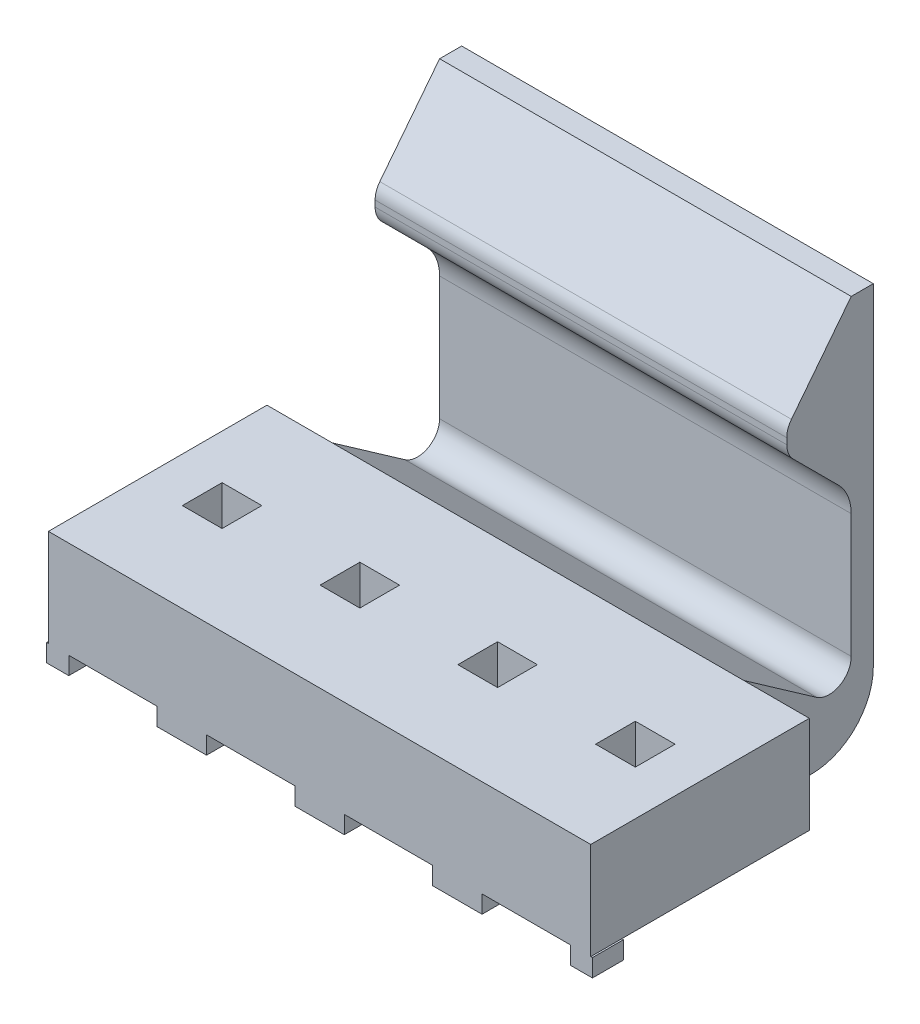
SolidWorks part; units mm, degrees
material "ABS"
ref_plane "Front Plane" through (0, 0, 0) normal (0, 0, 1) x (1, 0, 0)
ref_plane "Top Plane" through (0, 0, 0) normal (0, 1, 0) x (1, 0, 0)
ref_plane "Right Plane" through (0, 0, 0) normal (1, 0, 0) x (0, 0, -1)
sketch "Sketch51" plane through (0, 0, 0) normal (1, 0, 0) x (0, 0, -1)
  line L9 (3.1433, 1.397) -> (3.1432, -1.397)
  line L42 (-3.1432, -1.397) -> (3.1432, -1.397)
  line L44 (3.1433, 1.397) -> (-3.1433, 1.397)
  line L45 (-3.1433, 1.397) -> (-3.1432, -1.397)
  dimension "D1" = 2.794
  dimension "D2" = 6.2865
extrude "Boss-Extrude23" add sketch "Sketch51" along normal mid plane 15.6 separate body
sketch "Sketch49" plane through (0, 1.397, 0) normal (0, 1, 0) x (1, 0, 0)
  line L0 (7.8, 0) -> (5.9858, 0) construction
  line L1 (7.8, 3.1433) -> (7.8, -3.1433) construction
  line L16 (1.4097, -0.575) -> (2.5527, -0.575)
  line L17 (2.5527, -0.575) -> (2.5527, 0.568)
  line L18 (2.5527, 0.568) -> (1.4097, 0.568)
  line L19 (1.4097, 0.568) -> (1.4097, -0.575)
  line L20 (5.3721, -0.575) -> (6.5151, -0.575)
  line L21 (6.5151, -0.575) -> (6.5151, 0.568)
  line L22 (6.5151, 0.568) -> (5.3721, 0.568)
  line L23 (5.3721, 0.568) -> (5.3721, -0.575)
  line L24 (-2.5527, -0.575) -> (-1.4097, -0.575)
  line L25 (-1.4097, -0.575) -> (-1.4097, 0.568)
  line L26 (-1.4097, 0.568) -> (-2.5527, 0.568)
  line L27 (-2.5527, 0.568) -> (-2.5527, -0.575)
  line L28 (-6.5151, -0.575) -> (-5.3721, -0.575)
  line L29 (-5.3721, -0.575) -> (-5.3721, 0.568)
  line L30 (-5.3721, 0.568) -> (-6.5151, 0.568)
  line L31 (-6.5151, 0.568) -> (-6.5151, -0.575)
  line L34 (1.4097, -0.0035) -> (-1.4097, -0.0035) construction
  line L35 (0, 0) -> (0, -0.0035) construction
  dimension "D2" = 1.143
  dimension "D4" = 2.8194
  dimension "D5" = 2.8194
  dimension "D6" = 2.8194
extrude "Cut-Extrude22" cut sketch "Sketch49" against normal through all
sketch "Sketch50" plane through (0, 0, 0) normal (1, 0, 0) x (0, 0, -1)
  line L0 (3.1432, -1.397) -> (3.1433, 1.397) construction
  line L20 (3.1432, -1.905) -> (5.0863, -1.905)
  line L21 (6.8644, -0.127) -> (6.8644, 9.4234)
  line L22 (6.8644, 9.4234) -> (6.2293, 9.4234)
  line L23 (6.2293, 9.4234) -> (4.5098, 7.2224)
  line L24 (4.3751, 6.8315) -> (4.3751, 6.6552)
  line L25 (4.5611, 6.2062) -> (5.8574, 4.9099)
  line L26 (6.2293, 4.0119) -> (6.2293, 0.4559)
  line L27 (5.2301, -0.0642) -> (3.1433, 1.397)
  line L28 (3.1433, 1.397) -> (3.1432, -1.905)
  arc A10 (5.0863, -1.905) -> (6.8644, -0.127) centre (5.0863, -0.127) ccw
  arc A11 (4.5098, 7.2224) -> (4.3751, 6.8315) centre (5.0101, 6.8315) ccw
  arc A12 (4.3751, 6.6552) -> (4.5611, 6.2062) centre (5.0101, 6.6552) ccw
  arc A13 (6.2293, 4.0119) -> (5.8574, 4.9099) centre (4.9593, 4.0119) ccw
  arc A14 (5.2301, -0.0642) -> (6.2293, 0.4559) centre (5.5943, 0.4559) ccw
  dimension "D4" = 1.778
  dimension "D5" = 0.635
  dimension "D7" = 2.4511
  dimension "D8" = 1.27
  dimension "D13" = 0.635
  dimension "D14" = 2.4892
  dimension "D1" = 3.302
  dimension "D2" = 55
  dimension "D3" = 1.9431
  dimension "D6" = 3.556
  dimension "D9" = 45
  dimension "D10" = 9.5504
  dimension "D11" = 0.635
  dimension "D12" = 52
extrude "Boss-Extrude24" add sketch "Sketch50" along normal mid plane 11.84
sketch "Sketch52" plane through (0, -1.397, 0) normal (0, 1, 0) x (1, 0, 0)
  line L20 (7.8486, -3.1432) -> (7.2136, -3.1433)
  line L21 (7.2136, -3.1433) -> (7.2136, -2.2543)
  line L22 (7.2136, -2.2543) -> (7.8486, -2.2543)
  line L23 (7.8486, -2.2543) -> (7.8486, -3.1432)
  line L24 (0.7112, -3.1432) -> (-0.7112, -3.1432)
  line L25 (-0.7112, -3.1432) -> (-0.7112, -2.2543)
  line L26 (-0.7112, -2.2543) -> (0.7112, -2.2543)
  line L27 (0.7112, -2.2543) -> (0.7112, -3.1432)
  line L28 (4.6736, -3.1432) -> (3.2512, -3.1432)
  line L29 (3.2512, -3.1432) -> (3.2512, -2.2543)
  line L30 (3.2512, -2.2543) -> (4.6736, -2.2543)
  line L31 (4.6736, -2.2543) -> (4.6736, -3.1432)
  line L32 (-3.2512, -3.1432) -> (-4.6736, -3.1432)
  line L33 (-4.6736, -3.1432) -> (-4.6736, -2.2543)
  line L34 (-4.6736, -2.2543) -> (-3.2512, -2.2543)
  line L35 (-3.2512, -2.2543) -> (-3.2512, -3.1432)
  line L36 (-7.8486, -2.2543) -> (-7.2136, -2.2543)
  line L37 (-7.2136, -2.2543) -> (-7.2136, -3.1433)
  line L38 (-7.2136, -3.1433) -> (-7.8486, -3.1432)
  line L39 (-7.8486, -3.1432) -> (-7.8486, -2.2543)
extrude "Boss-Extrude25" add sketch "Sketch52" against normal blind 0.508
scale "Scale1" scale about centroid uniform scaling yes scale factor 0.654
ref_axis "Axis1" through (5.1012, 1.4051, -0.871) along (-1, 0, 0)
ref_plane "Plane1" through (0, 0, -0.871) normal (0, 0, 1) x (1, 0, 0)
